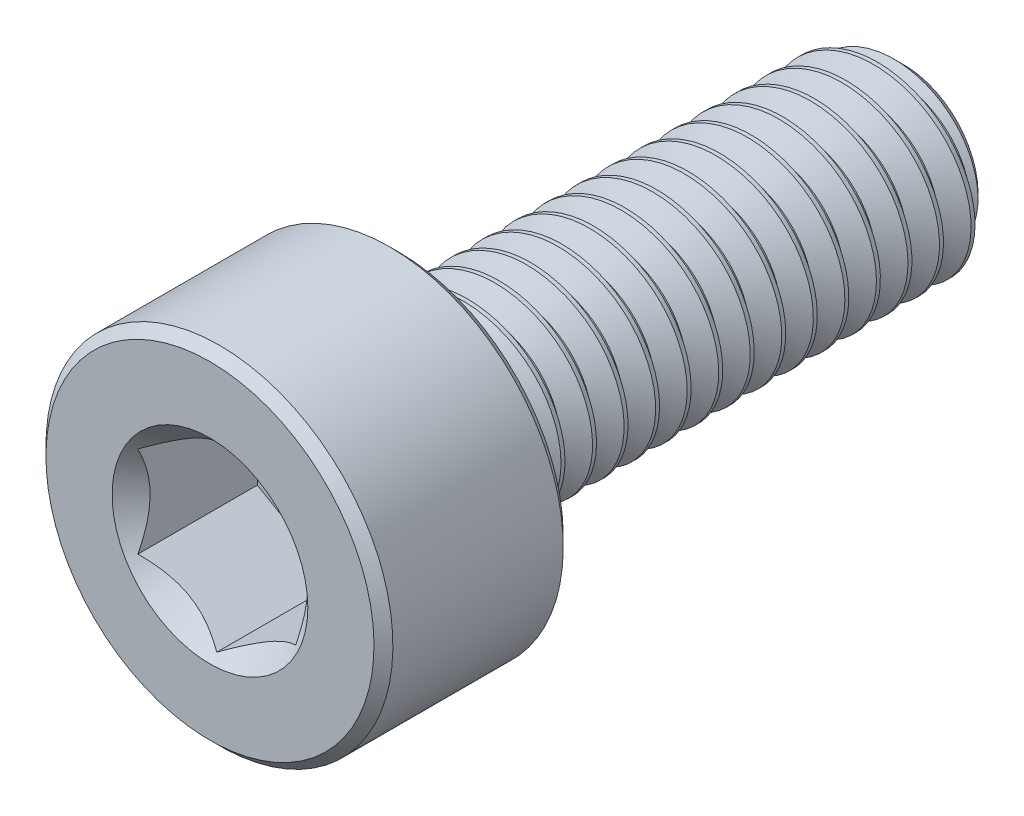
SolidWorks part; units mm, degrees
material "AISI 1020"
ref_plane "Front Plane" through (0, 0, 0) normal (0, 0, 1) x (1, 0, 0)
ref_plane "Top Plane" through (0, 0, 0) normal (0, 1, 0) x (1, 0, 0)
ref_plane "Right Plane" through (0, 0, 0) normal (1, 0, 0) x (0, 0, -1)
sketch "Sketch1" plane through (0, 0, 0) normal (1, 0, 0) x (0, 0, -1)
  line L0 (-5.5, 0) -> (5.5, 0) construction
  line L1 (5.5, 0) -> (5.5, 1.1752) construction
  line L2 (5.5, 1.1752) -> (5.1752, 1.5) construction
  line L3 (5.1752, 1.5) -> (5.125, 1.5) construction
  line L4 (5.125, 1.5) -> (-2.5, 1.5) construction
  line L5 (-2.5, 1.5) -> (-2.5, 2.75) construction
  line L6 (-2.5, 2.75) -> (-5.5, 2.75) construction
  line L7 (-5.5, 2.75) -> (-5.5, 0) construction
  line L8 (5.5, 1.1752) -> (5.5, 1.5) construction
  line L9 (5.4687, 1.5541) -> (5.7187, 1.1211) construction
  line L10 (5.7187, 1.1211) -> (5.9687, 1.5541) construction
  line L11 (5.9687, 1.5541) -> (5.4687, 1.5541) construction
  line L12 (5.7187, 1.5541) -> (5.7187, 1.5) construction
  line L13 (5.7187, 1.1211) -> (5.7187, 1.1752) construction
  line L14 (5.6875, 1.1752) -> (5.75, 1.1752) construction
  line L15 (5.5, 1.5) -> (5.9375, 1.5) construction
  line L16 (5.4844, 1.5271) -> (5.9531, 1.5271) construction
  line L17 (5.5, 0) -> (5.5, -1.5) construction
  line L18 (-2.65, 2.75) -> (-2.5, 2.6) construction
  line L19 (-5.35, 2.75) -> (-5.5, 2.6) construction
  line L20 (-2.5, 1.5) -> (-2.5, 0) construction
  line L21 (-2.5, 0.75) -> (0.1667, 0.75) construction
  line L22 (0.1667, 0.75) -> (2.8333, 0.75) construction
  line L23 (2.8333, 0.75) -> (5.5, 0.75) construction
  line L24 (0.1667, 0.75) -> (0.1667, 1.5) construction
  line L25 (0.1667, 1.5) -> (0.1667, 2.75) construction
  line L26 (2.8333, 0.75) -> (2.8333, 2.75) construction
  point P0 (-5.5, 1.25)
  point P3 (4.25, 1.5)
  point P4 (0, 0)
  point P18 (2.8333, 1.5)
  point P22 (5.7187, 1.1752)
  point P24 (5.125, 1.5)
  point P25 (5.7187, 1.5)
  point P28 (5.7187, 1.5271)
  point P29 (4.25, -1.5)
  point P30 (0.1667, 1.5)
  point P31 (-4, 2.75)
  point P37 (-3.025, 2.75)
  point P38 (-5.275, 2.75)
  point P45 (0.1667, 0.75)
  point P46 (2.8333, 0.75)
  dimension "D2" = 0.0625
  dimension "D7" = 0.15
  dimension "D8" = 0.15
  dimension "D9" = 0.15
  dimension "D10" = 0.075
  dimension "D11" = 0.375
  dimension "Drive Size" = 2.5
  dimension "Head Diameter" = 5.5
  dimension "Head Height" = 3
  dimension "Thread Pitch" = 0.5
  dimension "Thread Dia" = 3
  dimension "Length" = 8
  dimension "D12" = 0.375
  dimension "D4" = 1.25
  dimension "D3" = 45
sketch "Sketch2" plane through (0, 0, 0) normal (1, 0, 0) x (0, 0, -1)
  line L0 (-5.5, 0) -> (-5.5, 2.6)
  line L1 (-5.35, 2.75) -> (-2.65, 2.75)
  line L2 (-2.5, 2.6) -> (-2.5, 1.65)
  line L4 (5.1752, 1.5) -> (5.5, 1.1752)
  line L5 (5.5, 1.1752) -> (5.5, 0)
  line L6 (-2.5, 2.75) -> (-5.5, 2.75) construction
  line L7 (5.5, 0) -> (-5.5, 0)
  line L8 (-5.35, 2.75) -> (-5.5, 2.6) construction
  line L10 (-5.35, 2.75) -> (-5.5, 2.6)
  line L14 (-2.65, 2.75) -> (-2.5, 2.6) construction
  line L16 (-2.65, 2.75) -> (-2.5, 2.6)
  line L17 (-2.5, 1.5) -> (-2.5, 2.75) construction
  line L19 (-2.35, 1.5) -> (5.1752, 1.5)
  line L20 (5.125, 1.5) -> (-2.5, 1.5) construction
  arc A1 (-2.5, 1.65) -> (-2.35, 1.5) centre (-2.35, 1.65) ccw
  dimension "D3" = 0.15
revolve "Revolve1" add sketch "Sketch2" angle 360 about L7
sketch "Sketch3" plane through (0, 0, 5.5) normal (0, 0, 1) x (1, 0, 0)
  line L1 (1.25, -0.7217) -> (1.25, 0.7217)
  line L2 (1.25, 0.7217) -> (0, 1.4434)
  line L3 (0, 1.4434) -> (-1.25, 0.7217)
  line L4 (-1.25, 0.7217) -> (-1.25, -0.7217)
  line L5 (-1.25, -0.7217) -> (0, -1.4434)
  line L6 (0, -1.4434) -> (1.25, -0.7217)
  circle A0 centre (0, 0) radius 1.25 construction
  circle A1 centre (0, 0) radius 2.75 construction
  circle A2 centre (0, 0) radius 2.75 construction
  circle A3 centre (0, 0) radius 1.4434 construction
  point P13 (0, 0)
  dimension "D1" = 2.8868
extrude "Cut-Extrude1" cut sketch "Sketch3" against normal offset from surface (2 mm away) 1 up to face at (0, 2.6, 2.5)
sketch "Sketch4" plane through (0, 0, 5.5) normal (0, 0, 1) x (1, 0, 0)
  circle A0 centre (0, 0) radius 1.5516
  dimension "D1" = 3.1033
extrude "Cut-Extrude2" cut sketch "Sketch4" against normal up to vertex (1.5 mm away) draft 45 up to point (0, 2.75, 4)
sketch "Sketch11" plane through (0, 0, 0) normal (1, 0, 0) x (0, 0, -1)
  line L0 (-5.5, 0) -> (5.5, 0) construction
  line L1 (-5.5, 0) -> (5.5, 0) construction
  line L2 (-1, 0) -> (-1, 1.5) construction
  line L3 (5.125, 1.5) -> (-2.5, 1.5) construction
  line L4 (4, 0) -> (4, 1.5) construction
  line L6 (5.5, 1.1752) -> (5.5, 1.5) construction
  point P2 (-1, 0)
  point P3 (4, 0)
  dimension "D1" = 1.5
  dimension "D2" = 1.5
sketch "Sketch6" plane through (0, 0, -5.5) normal (0, 0, -1) x (-1, 0, 0)
  circle A0 centre (0, 0) radius 1.5
curve "Helix/Spiral1" pitch 0.5 height 8.5 radius 1.5 centre (0, 0, -5.5) axis (0, 0, 1) start towards (0, 1, 0)
sketch "Sketch10" plane through (0, 0, 0) normal (1, 0, 0) x (0, 0, -1)
  line L0 (-2.35, -2.75) -> (-2.35, 2.75)
  line L5 (-5.5, 0) -> (5.5, 0) construction
  line L6 (-2.35, 1.5) -> (-2.35, -1.5) construction
  point P3 (-2.35, 0)
split "Split1" trim tools "Sketch10" bodies to split 106 resulting bodies 114 115
sketch "Sketch7" plane through (0, 0, 0) normal (1, 0, 0) x (0, 0, -1)
  line L0 (5.4844, 1.5271) -> (5.9531, 1.5271)
  line L1 (5.9531, 1.5271) -> (5.75, 1.1752)
  line L2 (5.75, 1.1752) -> (5.6875, 1.1752)
  line L3 (5.6875, 1.1752) -> (5.4844, 1.5271)
sweep "Cut-Sweep1" cut profiles "Sketch7" path "Helix/Spiral1" align with end faces yes
sketch "Sketch8" plane through (0, 0, 0) normal (1, 0, 0) x (0, 0, -1)
  line L0 (-2.5, 0) -> (-2.5, 1.5)
  line L1 (-2.35, -1.5) -> (-2.35, 1.5) construction
  line L2 (-2.5, 1.5) -> (-2.35, 1.5)
  line L4 (-2.35, 1.5) -> (-1.484, 0)
  line L5 (-1.484, 0) -> (-2.5, 0)
  line L6 (5.125, 1.5) -> (-2.5, 1.5) construction
  line L7 (-5.5, 0) -> (5.5, 0) construction
  dimension "D1" = 60
revolve "Revolve2" add sketch "Sketch8" angle 360 about L5
equation "\"D2@Sketch1\" = \"Thread Pitch@Sketch1\" / 8"
equation "\"D4@Helix/Spiral1\" = \"Thread Pitch@Sketch1\""
equation "\"D7@Sketch1\" = \"Head Height@Sketch1\" * .05"
equation "\"D8@Sketch1\"=\"D7@Sketch1\""
equation "\"D9@Sketch1\"=\"D7@Sketch1\""
equation "\"D10@Sketch1\"=\"D7@Sketch1\"/2"
equation "\"D11@Sketch1\"=\"D10@Sketch1\"*5"
equation "\"D4@Sketch1\"=\"Thread Pitch@Sketch1\"*2.5"
equation "\"D12@Sketch1\"=\"Thread Pitch@Sketch1\"*.75"
equation "\"D3@Helix/Spiral1\"=\"Length@Sketch1\"+\"Thread Pitch@Sketch1\""
equation "\"D3@Sketch2\"=\"Thread Dia@Sketch1\"*0.05"
equation "\"D1@Sketch11\"=\"Length@Sketch1\"*0.1875"
equation "\"D2@Sketch11\"=\"D1@Sketch11\""
equation "\"D1@Sketch4\"=\"D1@Sketch3\"*1.075"
